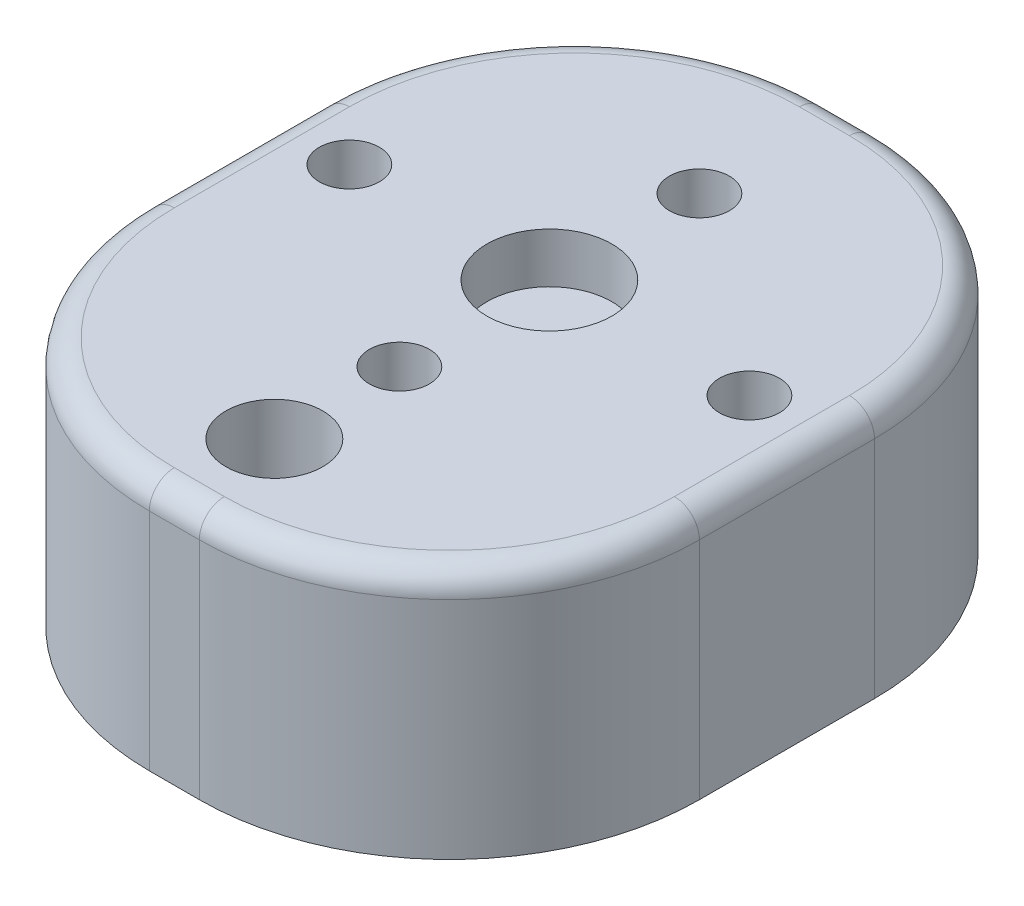
SolidWorks part; units mm, degrees
ref_plane "Plan de face" through (0, 0, 0) normal (0, 0, 1) x (1, 0, 0)
ref_plane "Plan de dessus" through (0, 0, 0) normal (0, 1, 0) x (1, 0, 0)
ref_plane "Plan de droite" through (0, 0, 0) normal (1, 0, 0) x (0, 0, -1)
sketch "Esquisse1" plane through (0, 0, 0) normal (0, 0, 1) x (1, 0, 0)
  line L1 (0, 0) -> (22, 0)
  line L2 (0, 0) -> (0, 10)
  line L3 (0, 10) -> (22, 10)
  line L4 (22, 0) -> (22, 10)
  arc A0 (6, 0) -> (16, 0) centre (11, 0) cw
  dimension "D3" = 5
  dimension "D1" = 22
  dimension "D2" = 10
  dimension "D4" = 11
extrude "Boss.-Extru.1" add sketch "Esquisse1" along normal blind 22 contours L1 A0 L4 L3 L2 region at (11, 5.6253, 0)
hole_wizard "Dégagement M21" positions "Esquisse2" profile "Esquisse4" hole size "M2" standard "ISO" end condition through all
sketch "Esquisse2" plane through (0, 10, 0) normal (0, 1, 0) x (1, 0, 0)
  line L0 (0, -22) -> (0, 0) construction
  line L3 (11, 5.9602) -> (11, -38.6048) construction
  line L5 (0, 0) -> (22, 0) construction
  point P0 (11, -6)
  point P2 (11, -18)
  point P4 (3, -12)
  point P6 (19, -12)
  dimension "D1" = 11
  dimension "D2" = 12
  dimension "D3" = 16
  dimension "D4" = 11
  dimension "D5" = 8
  dimension "D6" = 6
  dimension "D7" = 6
  dimension "D8" = 6
sketch "Esquisse4" plane through (11, 10, 6) normal (1, 0, 0) x (0, 0, 1)
  line L0 (0, 0) -> (0, 10)
  line L1 (0, 10) -> (1.2, 10)
  line L2 (1.2, 10) -> (1.2, 0)
  line L5 (1.2, 0) -> (0, 0)
  line L11 (0, -6.35) -> (0, 107.95) construction
  dimension "Diamètre du perçage jusqu'au prochain" = 2.4
  dimension "Profondeur du perçage jusqu'au prochain" = 10
sketch "Esquisse5" plane through (0, 0, 22) normal (0, 0, 1) x (1, 0, 0)
  line L1 (0, 0) -> (22, 0)
  line L2 (0, 0) -> (0, 10)
  line L3 (0, 10) -> (22, 10)
  line L4 (22, 0) -> (22, 10)
extrude "Boss.-Extru.2" add sketch "Esquisse5" along normal blind 5
fillet "Congé1" radius 10 4 edges at (0, 5, 0) (0, 5, 27) (22, 5, 0) (22, 5, 27)
fillet "Congé3" radius 1 8 edges at (11, 10, 27) (11, 10, 0) (2.9289, 10, 2.9289) (0, 10, 13.5) (2.9289, 10, 24.0711) (19.0711, 10, 24.0711) (22, 10, 13.5) (19.0711, 10, 2.9289)
sketch "Esquisse10" plane through (0, 0, 22) normal (0, 0, -1) x (-1, 0, 0)
  line L0 (-6, 0) -> (-16, 0) construction
  line L1 (-7, 0) -> (-15, 0)
  arc A0 (-15, 0) -> (-7, 0) centre (-11, 0) cw
  dimension "D1" = 4
  dimension "D2" = 5
extrude "Enlèv. mat.-Extru.2" cut sketch "Esquisse10" against normal blind 3
sketch "Esquisse12" plane through (0, 10, 0) normal (0, 1, 0) x (1, 0, 0)
  line L0 (0, -17) -> (0, -10) construction
  line L2 (10, 0) -> (12, 0) construction
  circle A0 centre (11, -23) radius 1.9376
  dimension "D1" = 11
  dimension "D2" = 23
extrude "Enlèv. mat.-Extru.3" cut sketch "Esquisse12" against normal through all
sketch "Esquisse13" plane through (0, 10, 0) normal (0, 1, 0) x (1, 0, 0)
  line L0 (22, -10) -> (22, -17) construction
  line L1 (10, 0) -> (12, 0) construction
  circle A0 centre (11, -12) radius 2.5
  dimension "D3" = 5
  dimension "D1" = 11
  dimension "D2" = 12
extrude "Enlèv. mat.-Extru.4" cut sketch "Esquisse13" against normal blind 2
sketch "Esquisse15" plane through (0, 0, 0) normal (0, -1, 0) x (1, 0, 0)
  circle A0 centre (11, 18) radius 2.5
  circle A1 centre (11, 6) radius 2.5
  dimension "D1" = 5
  dimension "D2" = 5
extrude "Enlèv. mat.-Extru.5" cut sketch "Esquisse15" against normal blind 7
equation "\"D4@Esquisse1\"=\"D1@Esquisse1\"/2"
